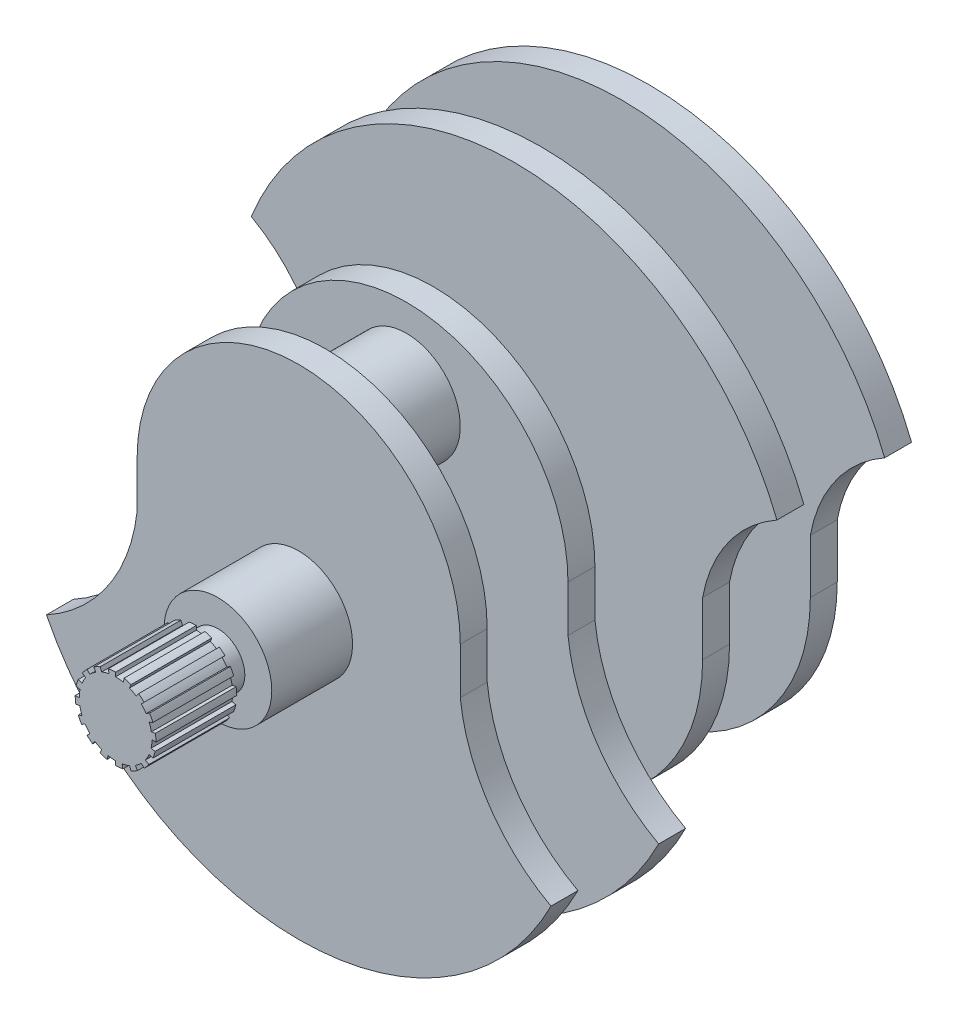
SolidWorks part; units mm, degrees
material "AISI 4340 Steel, normalized"
ref_plane "Front Plane" through (0, 0, 0) normal (0, 0, 1) x (1, 0, 0)
ref_plane "Top Plane" through (0, 0, 0) normal (0, 1, 0) x (1, 0, 0)
ref_plane "Right Plane" through (0, 0, 0) normal (1, 0, 0) x (0, 0, -1)
sketch "Sketch1" plane through (0, 0, 0) normal (0, 0, 1) x (1, 0, 0)
  circle A0 centre (0, 0) radius 20
  dimension "D1" = 20
extrude "Boss-Extrude1" add sketch "Sketch1" along normal blind 30
sketch "Sketch2" plane through (0, 0, 30) normal (0, 0, 1) x (1, 0, 0)
  circle A0 centre (0, 0) radius 10
  dimension "D1" = 10
extrude "Boss-Extrude2" add sketch "Sketch2" along normal blind 8
sketch "Sketch3" plane through (0, 0, 38) normal (0, 0, 1) x (1, 0, 0)
  circle A0 centre (0, 0) radius 15
  dimension "D1" = 15
extrude "Boss-Extrude3" add sketch "Sketch3" along normal blind 30
sketch "Sketch5" plane through (0, 0, 68) normal (0, 0, 1) x (1, 0, 0)
  line L0 (0, 15) -> (0, 13.5)
  line L1 (2.8421, 13.1974) -> (3.1579, 14.6638)
  circle A0 centre (0, 0) radius 15 construction
  arc A1 (0, 13.5) -> (2.8421, 13.1974) centre (0, 0) cw
  arc A2 (3.1579, 14.6638) -> (0, 15) centre (0, 0) ccw
  circle A3 centre (0, 0) radius 15
  point P8 (0, 14.25)
  circle M6 centre (0, 0) radius 15
  dimension "D1" = 13.5
  dimension "D2" = 3
extrude "Cut-Extrude1" cut sketch "Sketch5" against normal up to next contours L0 A1 L1 M6 region at (1.507, 14.1564, 68)
pattern_circular "CirPattern1" count 16 over 360 about axis through (0, 0, 68) along (0, 0, 1) of "Cut-Extrude1"
sketch "Sketch8" plane through (0, 0, 0) normal (0, 0, -1) x (-1, 0, 0)
  line L0 (-60, 20) -> (-60, 2.7836)
  line L1 (60, 20) -> (60, 2.7836)
  arc A0 (60, 20) -> (-60, 20) centre (0, 20) ccw
  arc A5 (-93.6849, -47.4146) -> (93.6849, -47.4146) centre (0, 0) ccw
  arc A6 (-60, 2.7836) -> (-93.6849, -47.4146) centre (-125, 10) cw
  arc A7 (60, 2.7836) -> (93.6849, -47.4146) centre (125, 10) ccw
  dimension "D1" = 60
  dimension "D2" = 105
  dimension "D3" = 20
  dimension "D5" = 10
  dimension "D6" = 125
extrude "Boss-Extrude5" add sketch "Sketch8" along normal blind 10
sketch "Sketch9" plane through (0, 0, -10) normal (0, 0, -1) x (-1, 0, 0)
  circle A0 centre (0, 50) radius 20
  dimension "D2" = 20
  dimension "D1" = 50
extrude "Boss-Extrude6" add sketch "Sketch9" along normal blind 30
ref_plane "Plane4" through (0, 0, -80) normal (0, 0, -1) x (-1, 0, 0)
sketch "Sketch10" plane through (0, 0, -40) normal (0, 0, -1) x (-1, 0, 0)
  line L0 (-70, -20) -> (-70, 0)
  line L1 (70, -20) -> (70, 0)
  arc A0 (-70, -20) -> (70, -20) centre (0, -20) ccw
  arc A1 (-70, 0) -> (-97.598, 38.7251) centre (-125, -10) ccw
  arc A2 (70, 0) -> (97.598, 38.7251) centre (125, -10) cw
  arc A3 (-97.598, 38.7251) -> (97.598, 38.7251) centre (0, 0) cw
  point P1 (0, 0)
  point P10 (0, 0)
  dimension "D1" = 70
  dimension "D3" = 105
  dimension "D2" = 20
  dimension "D4" = 125
  dimension "D5" = 10
extrude "Boss-Extrude7" add sketch "Sketch10" along normal blind 10 from surface starting at plane "Plane4"
ref_plane "Plane3" through (0, 0, -120) normal (0, 0, -1) x (-1, 0, 0)
sketch "Sketch12" plane through (0, 0, -120) normal (0, 0, -1) x (-1, 0, 0)
  line L2 (70, -20) -> (70, 0)
  line L3 (70, -20) -> (70, 0)
  line L4 (-70, 0) -> (-70, -20)
  line L5 (-70, 0) -> (-70, -20)
  arc A12 (-70, -20) -> (70, -20) centre (0, -20) ccw
  arc A13 (97.598, 38.7251) -> (70, 0) centre (125, -10) ccw
  arc A14 (97.598, 38.7251) -> (-97.598, 38.7251) centre (0, 0) ccw
  arc A15 (-70, 0) -> (-97.598, 38.7251) centre (-125, -10) ccw
  arc A16 (-70, -20) -> (70, -20) centre (0, -20) ccw
  arc A17 (97.598, 38.7251) -> (70, 0) centre (125, -10) ccw
  arc A18 (97.598, 38.7251) -> (-97.598, 38.7251) centre (0, 0) ccw
  arc A19 (-70, 0) -> (-97.598, 38.7251) centre (-125, -10) ccw
  dimension "D1" = 0
extrude "Boss-Extrude8" add sketch "Sketch12" along normal blind 10
sketch "Sketch14" plane through (0, 0, -90) normal (0, 0, -1) x (-1, 0, 0)
  circle A0 centre (0, -50) radius 20
  dimension "D2" = 20
  dimension "D1" = 50
extrude "Boss-Extrude9" add sketch "Sketch14" along normal up to next
sketch "Sketch15" plane through (0, 0, -130) normal (0, 0, -1) x (-1, 0, 0)
  circle A1 centre (0, 0) radius 20
  circle A2 centre (0, 0) radius 20
  dimension "D1" = 0
extrude "Boss-Extrude10" add sketch "Sketch15" along normal blind 30
sketch "Sketch16" plane through (0, 0, -160) normal (0, 0, -1) x (-1, 0, 0)
  circle A1 centre (0, 0) radius 10
  circle A2 centre (0, 0) radius 10
  dimension "D1" = 0
extrude "Boss-Extrude11" add sketch "Sketch16" along normal blind 8
sketch "Sketch18" plane through (0, 0, -40) normal (0, 0, -1) x (-1, 0, 0)
  line L2 (-60, 20) -> (-60, 2.7836)
  line L3 (-60, 20) -> (-60, 2.7836)
  line L4 (60, 2.7836) -> (60, 20)
  line L5 (60, 2.7836) -> (60, 20)
  arc A4 (60, 20) -> (-60, 20) centre (0, 20) ccw
  arc A5 (-93.6849, -47.4146) -> (-60, 2.7836) centre (-125, 10) ccw
  arc A6 (-93.6849, -47.4146) -> (93.6849, -47.4146) centre (0, 0) ccw
  arc A7 (60, 2.7836) -> (93.6849, -47.4146) centre (125, 10) ccw
  arc A8 (60, 20) -> (-60, 20) centre (0, 20) ccw
  arc A9 (-93.6849, -47.4146) -> (-60, 2.7836) centre (-125, 10) ccw
  arc A10 (-93.6849, -47.4146) -> (93.6849, -47.4146) centre (0, 0) ccw
  arc A11 (60, 2.7836) -> (93.6849, -47.4146) centre (125, 10) ccw
  dimension "D1" = 0
extrude "Boss-Extrude12" add sketch "Sketch18" along normal blind 10
sketch "Sketch19" plane through (0, 0, -50) normal (0, 0, -1) x (-1, 0, 0)
  circle A1 centre (0, 0) radius 20
  circle A2 centre (0, 0) radius 20
  dimension "D1" = 0
extrude "Boss-Extrude13" add sketch "Sketch19" along normal blind 30
equation "\"Crank Radius\"= 50mm"
